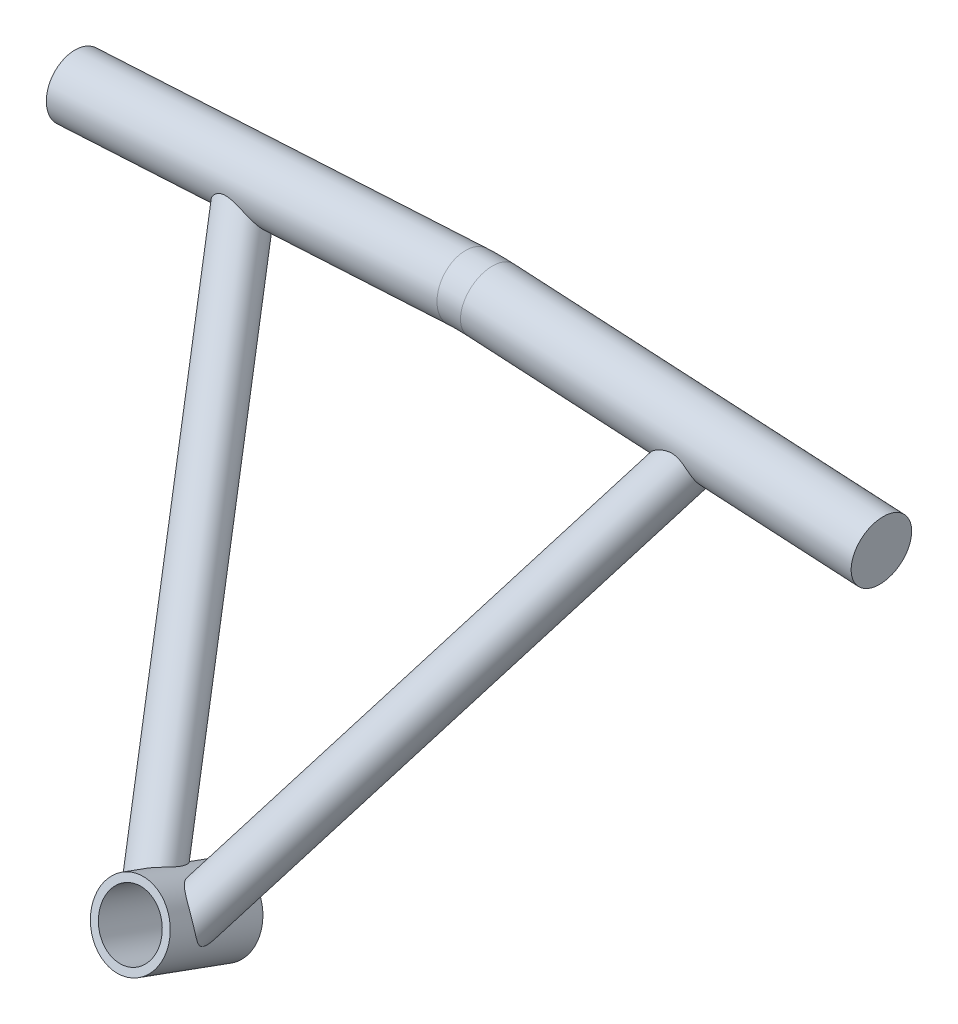
SolidWorks part; units mm, degrees
material "AISI 4130 Steel, normalized at 870C"
ref_plane "Front Plane" through (0, 0, 0) normal (0, 0, 1) x (1, 0, 0)
ref_plane "Top Plane" through (0, 0, 0) normal (0, 1, 0) x (1, 0, 0)
ref_plane "Right Plane" through (0, 0, 0) normal (1, 0, 0) x (0, 0, -1)
sketch "Sketch3" plane through (0, 0, 0) normal (0, 1, 0) x (1, 0, 0)
  line L0 (-5.08, -6.35) -> (5.08, -6.35) construction
  line L2 (0, -88.2205) -> (0, 88.2205) construction
  line L3 (5.08, 0) -> (-5.08, 0) construction
  point P10 (0, 0)
  dimension "D1" = 5.08
  dimension "D2" = 10.16
  dimension "D3" = 6.35
  dimension "D4" = 10.16
  dimension "D5" = 5.08
ref_plane "Plane1" through (0, 3.1268, 3.7263) normal (0, 0.6428, 0.766) x (1, 0, 0)
ref_plane "Plane3" through (0, 0, 0) normal (0, 0.342, 0.9397) x (-1, 0, 0)
sketch "Sketch1" plane through (0, 0, 0) normal (0, 0.342, 0.9397) x (1, 0, 0)
  circle A0 centre (0, 0) radius 15.875
  point P3 (0, 0)
  dimension "D1" = 31.75
extrude "Boss-Extrude1" add sketch "Sketch1" along normal mid plane 41.402 contours A0
sketch "Sketch4" plane through (0, 3.1268, 3.7263) normal (0, 0.6428, 0.766) x (1, 0, 0)
  line L0 (-5.08, -4.0817) -> (-98.06, 204.7548)
  line L2 (0, -24.1976) -> (0, 24.1976) construction
  point P4 (0, 0)
  dimension "D2" = 24
  dimension "D3" = 228.6
sweep "Sweep1" add path "Sketch4" circular profile diameter 19.05 parameters "D3"=19.05
sketch "Sketch15" plane through (0, 3.1268, 3.7263) normal (0, 0.6428, 0.766) x (1, 0, 0)
  line L0 (5.08, -4.0817) -> (98.06, 204.7548)
  line L1 (0, -88.2637) -> (0, 88.2637) construction
  point P5 (0, 0)
  point P6 (0, 0)
  dimension "D1" = 228.6
  dimension "D2" = 24
sweep "Sweep2" add path "Sketch15" circular profile diameter 19.05 parameters "D3"=19.05
sketch "Sketch2" plane through (0, -7.0802, -19.4526) normal (0, -0.342, -0.9397) x (-1, 0, 0)
  circle A0 centre (0, 0) radius 12.7
  dimension "D1" = 25.4
extrude "Cut-Extrude1" cut sketch "Sketch2" against normal up to next
sketch "Sketch36" plane through (-92.3038, 158.8145, -133.2612) normal (-0.4067, 0.6998, -0.5872) x (0.9135, 0.3116, -0.2614)
  circle A0 centre (-6.301, -4.8644) radius 7.9375
  dimension "D1" = 15.875
extrude "Cut-Extrude2" cut sketch "Sketch36" against normal blind 127
sketch "Sketch37" plane through (92.3038, 158.8145, -133.2612) normal (0.4067, 0.6998, -0.5872) x (0.9135, -0.3116, 0.2614)
  circle A0 centre (6.301, -4.8644) radius 7.9375
  dimension "D1" = 15.875
extrude "Cut-Extrude3" cut sketch "Sketch37" against normal blind 127
ref_plane "Plane2" through (0, 0, -127) normal (0, 0, 1) x (1, 0, 0)
sketch "Sketch40" plane through (-106.934, 0, -127) normal (0, 0, 1) x (1, 0, 0)
  line L2 (106.934, -61.3539) -> (106.934, 61.3539) construction
  line L3 (101.9947, 163.6927) -> (-62.0894, 154.562)
  line L4 (111.8733, 163.6927) -> (275.9574, 154.562)
  arc A0 (101.9947, 163.6927) -> (111.8733, 163.6927) centre (106.934, 74.93) cw
  point P0 (106.934, 163.83)
  point P7 (106.934, 163.83)
  dimension "D1" = 164.338
  dimension "D3" = 88.9
  dimension "D2" = 164.338
  dimension "D4" = 9.8786
sweep "Sweep3" add path "Sketch40" circular profile diameter 25.4 parameters "D3"=25.4
